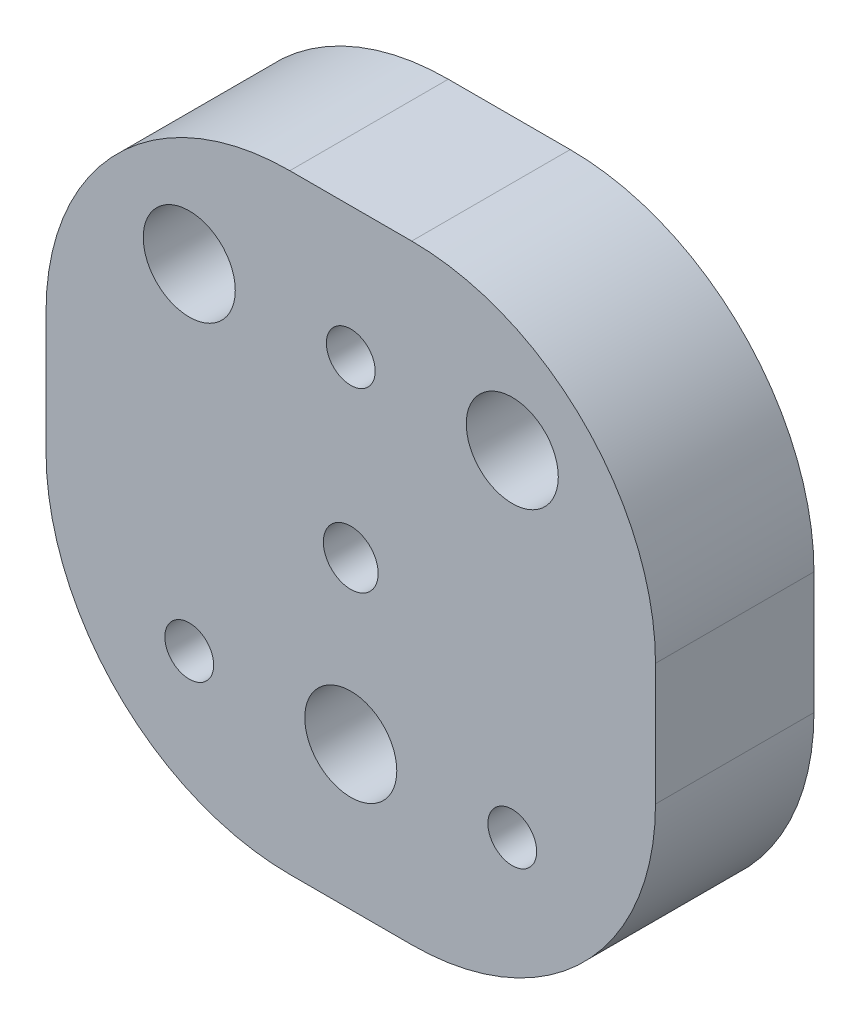
SolidWorks part; units mm, degrees
ref_plane "Front Plane" through (0, 0, 0) normal (0, 0, 1) x (1, 0, 0)
ref_plane "Top Plane" through (0, 0, 0) normal (0, 1, 0) x (1, 0, 0)
ref_plane "Right Plane" through (0, 0, 0) normal (1, 0, 0) x (0, 0, -1)
sketch "Sketch1" plane through (0, 0, 0) normal (0, 0, 1) x (1, 0, 0)
  line L1 (-50, -50) -> (50, -50)
  line L2 (-50, -50) -> (-50, 50)
  line L3 (-50, 50) -> (50, 50)
  line L4 (50, -50) -> (50, 50)
  line L5 (-50, -50) -> (50, 50) construction
  line L6 (-50, 50) -> (50, -50) construction
  point P0 (0, 0)
  dimension "D1" = 100
extrude "Boss-Extrude1" add sketch "Sketch1" along normal blind 26
sketch "Sketch2" plane through (0, 0, 26) normal (0, 0, 1) x (1, 0, 0)
  circle A0 centre (0, 28.5) radius 4.005
  circle A1 centre (-26.5, -26.5) radius 4.005
  circle A2 centre (26.5, -26.5) radius 4.005
  circle A3 centre (0, 0) radius 4.5
  dimension "D1" = 8.01
  dimension "D2" = 9
extrude "Cut-Extrude1" cut sketch "Sketch2" against normal offset from surface (23 mm away) 3 up to face at (0, 0, 0)
sketch "Sketch4" plane through (0, 0, 26) normal (0, 0, 1) x (1, 0, 0)
  circle A0 centre (-26.5, 28.5) radius 7.55
  circle A1 centre (26.5, 28.5) radius 7.55
  circle A2 centre (0, -26.5) radius 7.55
  dimension "D1" = 15.1
extrude "Cut-Extrude2" cut sketch "Sketch4" against normal offset from surface (24 mm away) 2 up to face at (0, 0, 0)
sketch "Sketch5" plane through (0, 0, 26) normal (0, 0, 1) x (1, 0, 0)
  circle A0 centre (-26.5, 28.5) radius 4.5
  circle A1 centre (26.5, 28.5) radius 4.5
  circle A2 centre (0, -26.5) radius 4.5
  dimension "D1" = 9
extrude "Cut-Extrude3" cut sketch "Sketch5" against normal through all both and the other way through all
fillet "Fillet1" radius 40 4 edges at (50, 50, 13) (-50, 50, 13) (-50, -50, 13) (50, -50, 13)
